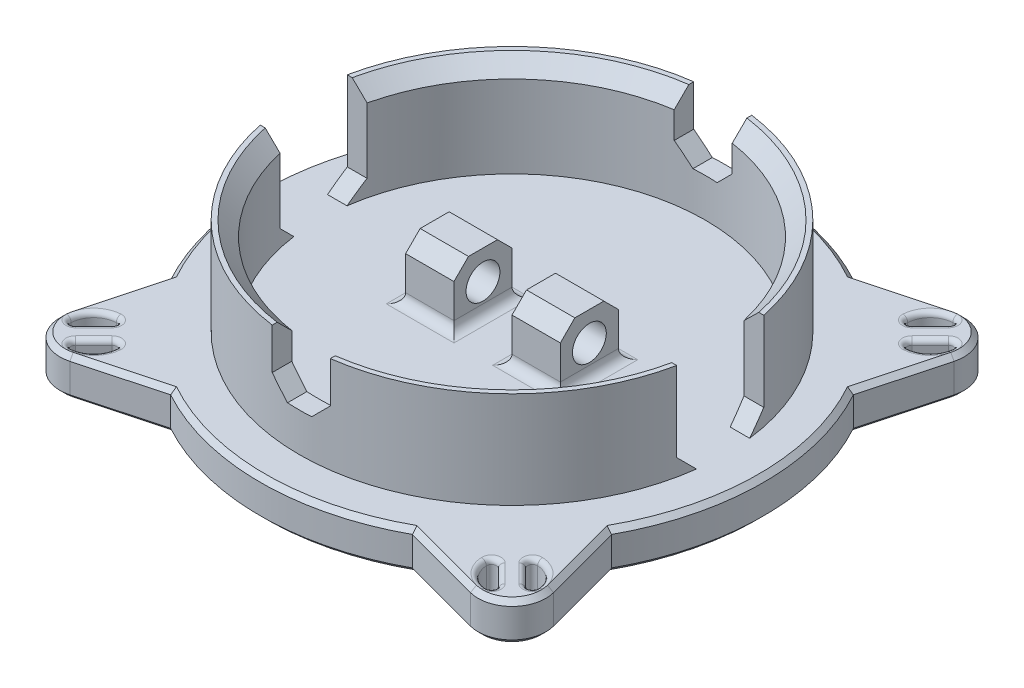
SolidWorks part; units mm, degrees
material "PLA"
ref_plane "Front Plane" through (0, 0, 0) normal (0, 0, 1) x (1, 0, 0)
ref_plane "Top Plane" through (0, 0, 0) normal (0, 1, 0) x (1, 0, 0)
ref_plane "Right Plane" through (0, 0, 0) normal (1, 0, 0) x (0, 0, -1)
sketch "Sketch1" plane through (0, 0, 0) normal (0, 1, 0) x (1, 0, 0)
  line L1 (21.625, -21.625) -> (-21.625, -21.625) construction
  line L2 (21.625, -21.625) -> (21.625, 21.625) construction
  line L3 (21.625, 21.625) -> (-21.625, 21.625) construction
  line L4 (-21.625, -21.625) -> (-21.625, 21.625) construction
  line L5 (21.625, -21.625) -> (-21.625, 21.625) construction
  line L6 (21.625, 21.625) -> (-21.625, -21.625) construction
  line L14 (-25.0052, -20.7171) -> (-22.798, -12.5)
  line L15 (-20.7171, -25.0052) -> (-12.5, -22.798)
  line L16 (20.7171, -25.0052) -> (12.5, -22.798)
  line L17 (25.0052, -20.7171) -> (22.798, -12.5)
  line L18 (25.0052, 20.7171) -> (22.798, 12.5)
  line L19 (20.7171, 25.0052) -> (12.5, 22.798)
  line L20 (-20.7171, 25.0052) -> (-12.5, 22.798)
  line L21 (-25.0052, 20.7171) -> (-22.798, 12.5)
  circle A0 centre (0, 0) radius 26 construction
  circle A1 centre (-21.625, 21.625) radius 3.5 construction
  circle A5 centre (21.625, 21.625) radius 3.5 construction
  circle A6 centre (21.625, -21.625) radius 3.5 construction
  circle A7 centre (-21.625, -21.625) radius 3.5 construction
  arc A9 (-20.7171, 25.0052) -> (-25.0052, 20.7171) centre (-21.625, 21.625) ccw
  arc A10 (20.7171, 25.0052) -> (25.0052, 20.7171) centre (21.625, 21.625) cw
  arc A11 (25.0052, -20.7171) -> (20.7171, -25.0052) centre (21.625, -21.625) cw
  arc A12 (-25.0052, -20.7171) -> (-20.7171, -25.0052) centre (-21.625, -21.625) ccw
  arc A13 (-12.5, 22.798) -> (12.5, 22.798) centre (0, 0) cw
  arc A14 (-22.798, 12.5) -> (-22.798, -12.5) centre (0, 0) ccw
  arc A15 (-12.5, -22.798) -> (12.5, -22.798) centre (0, 0) ccw
  arc A16 (22.798, 12.5) -> (22.798, -12.5) centre (0, 0) cw
  point P28 (-26, 0)
  point P45 (0, 26)
  point P46 (0, -26)
  dimension "D1" = 43.25
  dimension "D3" = 7
  dimension "D6" = 52
  dimension "D7" = 25
  dimension "D8" = 25
  dimension "D2" = 43.25
  dimension "D4" = 2
  dimension "D5" = 2
extrude "Boss-Extrude1" add sketch "Sketch1" along normal blind 4
sketch "Sketch2" plane through (0, 4, 0) normal (0, 1, 0) x (1, 0, 0)
  circle A0 centre (0, 0) radius 22
  circle A1 centre (0, 0) radius 20
  dimension "D1" = 44
  dimension "D2" = 2
extrude "Boss-Extrude2" add sketch "Sketch2" along normal blind 10
chamfer "Chamfer1" distance 1.5 angle 45 1 edges at (0, 14, 20)
chamfer "Chamfer2" distance 0.5 angle 45 32 edges at (16.6085, 4, 23.9016) (0, 4, 26) (-16.6085, 4, 23.9016) (-24.0999, 4, 24.0999) (-23.9016, 4, 16.6085) (-26, 4, 0) (-23.9016, 4, -16.6085) (-24.0999, 4, -24.0999) (-16.6085, 4, -23.9016) (0, 4, -26) (16.6085, 4, -23.9016) (24.0999, 4, -24.0999) (23.9016, 4, -16.6085) (26, 4, 0) (23.9016, 4, 16.6085) (24.0999, 4, 24.0999) (23.9016, 0, 16.6085) (26, 0, 0) (23.9016, 0, -16.6085) (24.0999, 0, -24.0999) (16.6085, 0, -23.9016) (0, 0, -26) (-16.6085, 0, -23.9016) (-24.0999, 0, -24.0999) (-23.9016, 0, -16.6085) (-26, 0, 0) (-23.9016, 0, 16.6085) (-24.0999, 0, 24.0999) (-16.6085, 0, 23.9016) (0, 0, 26) (16.6085, 0, 23.9016) (24.0999, 0, 24.0999)
sketch "Sketch3" plane through (0, 0, 0) normal (1, 0, 0) x (0, 0, -1)
  line L0 (0, -1000) -> (0, 49000) construction
  line L1 (21.5, 14) -> (-21.5, 14) construction
  line L2 (-4.5, 14) -> (4.5, 14)
  line L3 (-4.5, 14) -> (-4.5, 4)
  line L4 (-4.5, 4) -> (4.5, 4)
  line L5 (4.5, 14) -> (4.5, 4)
  line L6 (22, 4) -> (-22, 4) construction
  point P9 (0, 14)
  dimension "D1" = 9
extrude "Cut-Extrude1" cut sketch "Sketch3" against normal through all both and the other way through all
sketch "Sketch4" plane through (0, 4, 0) normal (0, 1, 0) x (1, 0, 0)
  line L0 (-1000, 0) -> (49000, 0) construction
  line L2 (-8, -3) -> (-3, -3)
  line L3 (-8, -3) -> (-8, 3)
  line L4 (-8, 3) -> (-3, 3)
  line L5 (-3, -3) -> (-3, 3)
  line L6 (-8, -3) -> (-3, 3) construction
  line L7 (-8, 3) -> (-3, -3) construction
  line L8 (3, -3) -> (8, -3)
  line L9 (3, -3) -> (3, 3)
  line L10 (3, 3) -> (8, 3)
  line L11 (8, -3) -> (8, 3)
  line L12 (3, -3) -> (8, 3) construction
  line L13 (3, 3) -> (8, -3) construction
  point P1 (-5.5, 0)
  point P8 (5.5, 0)
  dimension "D1" = 6
  dimension "D2" = 5
  dimension "D3" = 3
  dimension "D4" = 3
extrude "Boss-Extrude3" add sketch "Sketch4" along normal blind 6
sketch "Sketch5" plane through (-8, 0, 0) normal (-1, 0, 0) x (0, 0, 1)
  line L0 (-3, 10) -> (3, 4) construction
  line L1 (3, 10) -> (-3, 4) construction
  circle A0 centre (0, 7) radius 1.75
  point P8 (0, 7)
  dimension "D1" = 3.5
extrude "Cut-Extrude2" cut sketch "Sketch5" against normal up to surface (16 mm away) up to face at (8, 7, 0)
chamfer "Chamfer3" distance 1.5 angle 45 4 edges at (5.5, 10, 3) (5.5, 10, -3) (-5.5, 10, -3) (-5.5, 10, 3)
ref_axis "Axis1" through (0, 10.5, 0) along (0, -1, 0)
sketch "Sketch14" plane through (0, 0, 0) normal (0, 1, 0) x (1, 0, 0)
  line L0 (0, 0) -> (-24.0999, 24.0999) construction
  line L1 (-23.9523, 22.5381) -> (-20.7119, 19.2977)
  line L2 (-22.5381, 23.9523) -> (-19.2977, 20.7119)
  arc A0 (-20.7171, 25.0052) -> (-25.0052, 20.7171) centre (-21.625, 21.625) ccw construction
  arc A2 (-23.9523, 22.5381) -> (-20.7119, 19.2977) centre (-21.625, 21.625) ccw
  arc A3 (-22.5381, 23.9523) -> (-19.2977, 20.7119) centre (-21.625, 21.625) cw
  point P11 (-23.3928, 19.8572)
  dimension "D1" = 1.5
  dimension "D2" = 2.5
  dimension "D3" = 3.5
extrude "Cut-Extrude9" cut sketch "Sketch14" along normal through all
sketch "Sketch17" plane through (0, 0, 0) normal (0, -1, 0) x (1, 0, 0)
  circle A0 centre (-21.625, -21.625) radius 2.5
  arc A1 (-20.7119, -19.2977) -> (-23.9523, -22.5381) centre (-21.625, -21.625) ccw construction
extrude "Cut-Extrude11" [suppressed] cut sketch "Sketch17" against normal blind 2 from surface
sketch "Sketch13" plane through (0, 4, 0) normal (0, 1, 0) x (1, 0, 0)
  line L0 (-21.625, 21.625) -> (0, 0) construction
  circle A0 centre (-21.625, 21.625) radius 3
  arc A4 (-20.8468, 24.5223) -> (-24.5223, 20.8468) centre (-21.625, 21.625) ccw construction
extrude "Cut-Extrude8" [suppressed] cut sketch "Sketch13" against normal blind 2 draft 12
mirror "Mirror1" about plane through (0, 0, 0) normal (0, 0, 1) of "Cut-Extrude9", "Cut-Extrude8"
mirror "Mirror2" about plane through (0, 0, 0) normal (1, 0, 0) of "Mirror1"
fillet "Fillet1" [suppressed] radius 0.4
fillet "Fillet3" [suppressed] radius 0.25
sketch "Sketch15" plane through (0, 0, 0) normal (0, 0, 1) x (1, 0, 0)
  line L0 (0, -1000) -> (0, 49000) construction
  line L1 (21.5349, 14) -> (-21.5349, 14) construction
  line L2 (-3, 8) -> (3, 8)
  line L3 (-3, 8) -> (-3, 14)
  line L4 (-3, 14) -> (3, 14)
  line L5 (3, 8) -> (3, 14)
  line L6 (-3, 8) -> (3, 14) construction
  line L7 (-3, 14) -> (3, 8) construction
  line L8 (3, 11.5) -> (3, 16) construction
  point P1 (0, 11)
extrude "Cut-Extrude10" cut sketch "Sketch15" against normal through all both and the other way through all
chamfer "Chamfer4" distance 1.75 angle 45 8 edges at (3, 8, -20.7841) (-3, 8, -20.7841) (20.511, 4, 4.5) (20.511, 4, -4.5) (-20.511, 4, 4.5) (-20.511, 4, -4.5) (-3, 8, 20.7841) (3, 8, 20.7841)
fillet "Fillet2" radius 1 8 edges at (-5.5, 4, -3) (5.5, 4, -3) (3, 4, 0) (8, 4, 0) (5.5, 4, 3) (-3, 4, 0) (-5.5, 4, 3) (-8, 4, 0)
fillet "Fillet4" radius 0.5 16 edges at (-22.5381, 2, 23.9523) (-23.9523, 2, 22.5381) (-19.2977, 2, 20.7119) (-20.7119, 2, 19.2977) (23.9523, 2, 22.5381) (22.5381, 2, 23.9523) (20.7119, 2, 19.2977) (19.2977, 2, 20.7119) (20.7119, 2, -19.2977) (19.2977, 2, -20.7119) (23.9523, 2, -22.5381) (22.5381, 2, -23.9523) (-19.2977, 2, -20.7119) (-20.7119, 2, -19.2977) (-22.5381, 2, -23.9523) (-23.9523, 2, -22.5381)
fillet "Fillet5" radius 0.5 64 edges at (-21.2945, 0, 19.4232) (-23.3928, 0, 19.8572) (-23.8268, 0, 21.9555) (-21.9555, 0, 23.8268) (-19.8572, 0, 23.3928) (-19.4232, 0, 21.2945) (-22.3321, 0, 20.9179) (-20.9179, 0, 22.3321) (-21.2945, 0, -19.4232) (-23.3928, 0, -19.8572) (-23.8268, 0, -21.9555) (-19.4232, 0, -21.2945) (-20.9179, 0, -22.3321) (-21.9555, 0, -23.8268) (-21.9555, 4, -23.8268) (-19.8572, 4, -23.3928) (-19.4232, 4, -21.2945) (-21.2945, 4, -19.4232) (-23.3928, 4, -19.8572) (-23.8268, 4, -21.9555) (21.9555, 0, -23.8268) (19.8572, 0, -23.3928) (19.4232, 0, -21.2945) (21.2945, 0, -19.4232) (23.3928, 0, -19.8572) (23.8268, 0, -21.9555) (21.2945, 4, -19.4232) (23.3928, 4, -19.8572) (23.8268, 4, -21.9555) (19.4232, 4, -21.2945) (20.9179, 4, -22.3321) (21.9555, 4, -23.8268) (21.2945, 0, 19.4232) (23.3928, 0, 19.8572) (23.8268, 0, 21.9555) (21.9555, 0, 23.8268) (19.8572, 0, 23.3928) (19.4232, 0, 21.2945) (23.8268, 4, 21.9555) (22.3321, 4, 20.9179) (21.2945, 4, 19.4232) (21.9555, 4, 23.8268) (19.8572, 4, 23.3928) (19.4232, 4, 21.2945) (-21.9555, 4, 23.8268) (-19.8572, 4, 23.3928) (-19.4232, 4, 21.2945) (-23.8268, 4, 21.9555) (-22.3321, 4, 20.9179) (-21.2945, 4, 19.4232) (-22.3321, 0, -20.9179) (-19.8572, 0, -23.3928) (-20.9179, 4, -22.3321) (-22.3321, 4, -20.9179) (20.9179, 0, -22.3321) (22.3321, 0, -20.9179) (22.3321, 4, -20.9179) (19.8572, 4, -23.3928) (22.3321, 0, 20.9179) (20.9179, 0, 22.3321) (23.3928, 4, 19.8572) (20.9179, 4, 22.3321) (-20.9179, 4, 22.3321) (-23.3928, 4, 19.8572)
